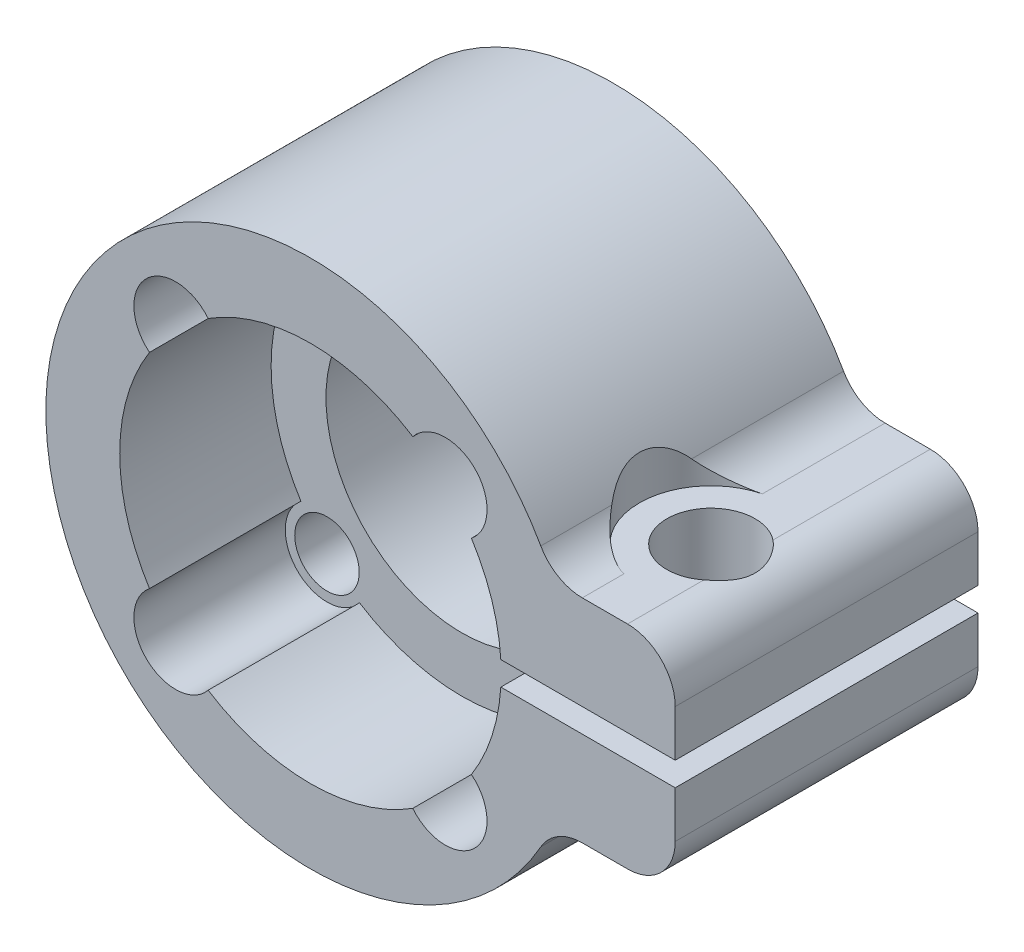
SolidWorks part; units mm, degrees
other "Defeature"
material "6061 Alloy"
ref_plane "Front Plane" through (0, 0, 0) normal (0, 0, 1) x (1, 0, 0)
ref_plane "Top Plane" through (0, 0, 0) normal (0, 1, 0) x (1, 0, 0)
ref_plane "Right Plane" through (0, 0, 0) normal (1, 0, 0) x (0, 0, -1)
sketch "Sketch1" plane through (0, 0, 0) normal (0, 0, 1) x (1, 0, 0)
  line L0 (-18.136, 0) -> (24.0528, 0) construction
  line L1 (0, 0) -> (0, 0.5)
  line L2 (0, 0.5) -> (15.3, 0.5)
  line L3 (15.3, 0.5) -> (15.3, 4.45)
  line L4 (15.3, 4.45) -> (11.4021, 4.45)
  line L5 (0, 0) -> (0, -0.5)
  line L6 (0, -0.5) -> (15.3, -0.5)
  line L7 (15.3, -0.5) -> (15.3, -4.45)
  line L8 (15.3, -4.45) -> (11.4021, -4.45)
  arc A0 (9.6613, 5.4653) -> (9.6613, -5.4653) centre (0, 0) ccw
  arc A1 (11.4021, -4.45) -> (9.6613, -5.4653) centre (11.4021, -6.45) ccw
  arc A2 (11.4021, 4.45) -> (9.6613, 5.4653) centre (11.4021, 6.45) cw
  point P5 (-11.1, 0)
  point P9 (10.1689, -4.45)
  point P12 (10.1689, 4.45)
  dimension "D1" = 22.2
  dimension "D2" = 8.9
  dimension "D5" = 2
  dimension "D3" = 1
  dimension "D4" = 26.4
extrude "Boss-Extrude1" add sketch "Sketch1" against normal mid plane 12.7
sketch "Sketch2" plane through (0, 0, -6.35) normal (0, 0, 1) x (1, 0, 0)
  line L0 (-5.6565, 5.6572) -> (5.6565, -5.6572) construction
  line L1 (5.6572, 5.6565) -> (-5.6572, -5.6565) construction
  line L2 (0, 0) -> (0, -8) construction
  circle A0 centre (0, 0) radius 8 construction
  circle A1 centre (5.6572, 5.6565) radius 1.85
  circle A2 centre (-5.6572, -5.6565) radius 1.85
  circle A3 centre (5.6565, -5.6572) radius 1.85
  circle A4 centre (-5.6565, 5.6572) radius 1.85
  dimension "D1" = 16
  dimension "D2" = 3.7
  dimension "D3" = 45.003
sketch "Sketch27" plane through (0, 0, 0) normal (0, 1, 0) x (1, 0, 0)
  line L0 (0, 6.35) -> (0, -6.35) construction
  line L1 (9.6613, 6.35) -> (-11.1, 6.35) construction
  line L2 (0, 6.35) -> (15.3, 6.35) construction
  line L3 (0, 6.35) -> (5.7, 6.35)
  line L4 (5.7, 6.35) -> (5.7, 0)
  line L5 (5.7, 0) -> (8, 0)
  line L6 (8, 0) -> (8, -6.35)
  line L7 (-11.1, -6.35) -> (9.6613, -6.35) construction
  line L8 (8, -6.35) -> (0, -6.35)
  line L9 (0, 6.35) -> (0, -6.35)
  dimension "D1" = 11.4
  dimension "D2" = 16
revolve "Cut-Revolve1" cut sketch "Sketch27" angle 360 about L0
hole_wizard "#6-32 Tapped Hole3" positions "3DSketch3" profile "Sketch5" tap size "#6-32" standard "ANSI Inch" end condition through all
sketch3d "3DSketch3"
  point P0 (-5.6565, 5.6572, -6.35)
  point P3 (5.6572, 5.6565, -6.35)
  point P6 (5.6565, -5.6572, -6.35)
  point P9 (-5.6572, -5.6565, -6.35)
sketch "Sketch5" plane through (-5.6565, 5.6572, -6.35) normal (1, 0, 0) x (0, 1, 0)
  line L0 (0, 0) -> (0, 12.7)
  line L1 (0, 12.7) -> (1.3525, 12.7)
  line L2 (1.3525, 12.7) -> (1.3525, 0)
  line L5 (1.3525, 0) -> (0, 0)
  line L11 (0, -6.35) -> (0, 107.95) construction
  dimension "Thru Tap Drill Dia." = 2.7051
  dimension "Thru Tap Drill Depth" = 12.7
cosmetic thread "Hole Thread11" parameters "D2"=3.5052
cosmetic thread "Hole Thread12" parameters "D2"=3.5052
cosmetic thread "Hole Thread13" parameters "D2"=3.5052
cosmetic thread "Hole Thread14" parameters "D2"=3.5052
sketch "Sketch14" plane through (0, 0.5, 0) normal (0, -1, 0) x (1, 0, 0)
  line L2 (15.3, -6.35) -> (15.3, 6.35) construction
  line L4 (11.4021, 6.35) -> (15.3, 6.35) construction
  circle A0 centre (12.15, 1.7) radius 1.85
  point P2 (14, 1.7)
  point P3 (12.15, -0.15)
  point P8 (12.15, 3.55)
  dimension "D1" = 3.7
  dimension "D2" = 1.3
  dimension "D3" = 2.8
extrude "Cut-Extrude6" cut sketch "Sketch14" against normal through all
hole_wizard "#6-32 Tapped Hole5" positions "Sketch19" profile "Sketch18" tap size "#6-32" standard "Ansi Inch"
sketch "Sketch19" plane through (0, -0.5, 0) normal (0, 1, 0) x (-1, 0, 0)
  circle A0 centre (-12.15, 1.7) radius 1.85 construction
  point P0 (-12.15, 1.7)
sketch "Sketch18" plane through (12.15, -0.5, 1.7) normal (1, 0, 0) x (0, 0, 1)
  line L0 (0, 0) -> (0, 51.6127)
  line L1 (0, 51.6127) -> (1.3525, 50.8)
  line L2 (1.3525, 50.8) -> (1.3525, 0)
  line L5 (1.3525, 0) -> (0, 0)
  line L10 (0, 51.6127) -> (-1.3526, 50.8) construction
  line L11 (0, -6.35) -> (0, 107.95) construction
  dimension "Tap Drill Dia." = 2.7051
  dimension "Tap Drill Depth" = 50.8
  dimension "Drill Angle" = 118
cosmetic thread "Hole Thread10" parameters "D1"=4.3212, "D2"=3.5052
sketch "Sketch24" plane through (19.75, 4.45, 0) normal (0, 1, 0) x (0, 0, -1)
  circle A0 centre (-1.7, 7.6) radius 3
  dimension "D1" = 6
extrude "Cut-Extrude26" cut sketch "Sketch24" along normal through all
fillet "Fillet1" radius 2 2 edges at (15.3, -4.45, 0) (15.3, 4.45, 0)
sketch "Sketch28" plane through (0, 0, 6.35) normal (0, 0, 1) x (1, 0, 0)
  circle A0 centre (5.6565, -5.6572) radius 1.75
  circle A1 centre (-5.6565, 5.6572) radius 1.75
  circle A2 centre (5.6572, 5.6565) radius 1.75
  circle A3 centre (-5.6572, -5.6565) radius 1.75
  dimension "D1" = 3.5
extrude "Cut-Extrude27" cut sketch "Sketch28" against normal up to surface (6.35 mm away) up to face at (1.2542, 0, 0)
